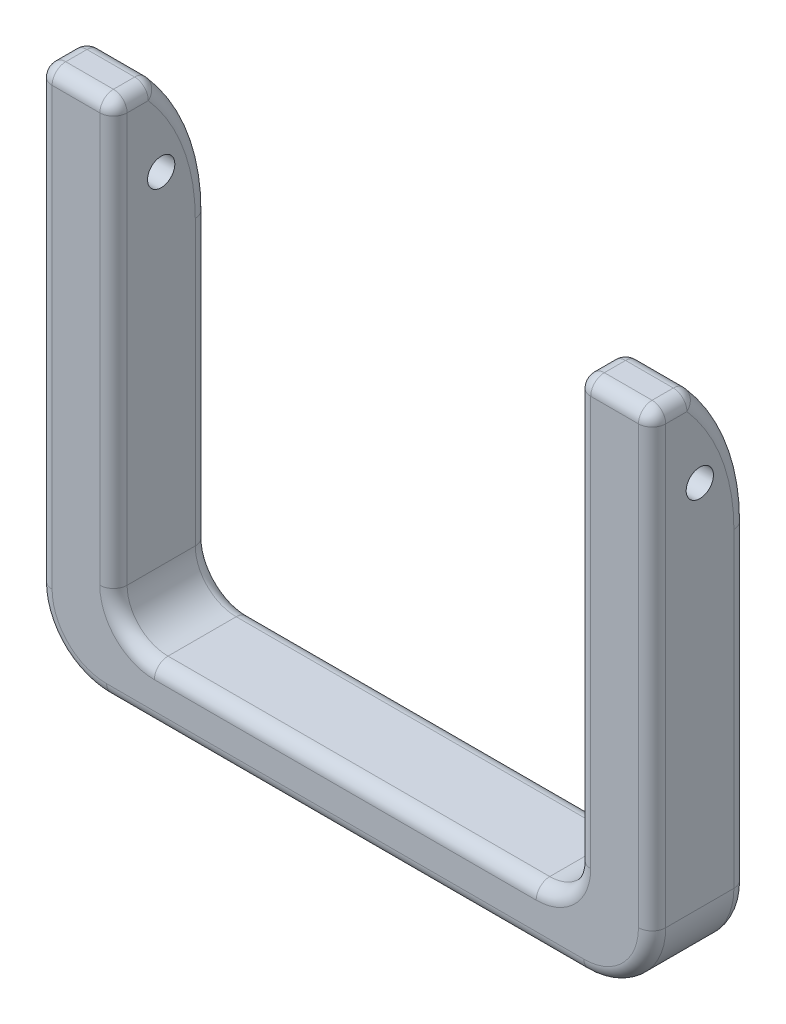
SolidWorks part; units mm, degrees
ref_plane "前视基准面" through (0, 0, 0) normal (0, 0, 1) x (1, 0, 0)
ref_plane "上视基准面" through (0, 0, 0) normal (0, 1, 0) x (1, 0, 0)
ref_plane "右视基准面" through (0, 0, 0) normal (1, 0, 0) x (0, 0, -1)
sketch "草图1" plane through (0, 0, 0) normal (0, 0, 1) x (1, 0, 0)
  line L0 (14, 0) -> (-14, 0)
  line L1 (-17, 3) -> (-17, 34)
  line L2 (-17, 34) -> (-22.5, 34)
  line L3 (-22.5, 34) -> (-22.5, 1)
  line L4 (-17.5, -4) -> (17.5, -4)
  line L5 (0, -4) -> (0, 0) construction
  line L6 (22.5, 34) -> (22.5, 1)
  line L7 (17, 34) -> (22.5, 34)
  line L8 (17, 3) -> (17, 34)
  arc A0 (17, 3) -> (14, 0) centre (14, 3) cw
  arc A1 (-14, 0) -> (-17, 3) centre (-14, 3) cw
  arc A2 (22.5, 1) -> (17.5, -4) centre (17.5, 1) cw
  arc A3 (-22.5, 1) -> (-17.5, -4) centre (-17.5, 1) ccw
  point P13 (17, 0)
  point P16 (-17, 0)
  point P19 (22.5, -4)
  point P22 (-22.5, -4)
  dimension "D5" = 3
  dimension "D6" = 5
  dimension "D1" = 5.5
  dimension "D2" = 38
  dimension "D3" = 4
  dimension "D4" = 17
extrude "凸台-拉伸1" add sketch "草图1" along normal blind 7
sketch "草图3" plane through (-22.5, 0, 0) normal (-1, 0, 0) x (0, 0, 1)
  line L0 (3.5, -4) -> (3.5, 28.7715) construction
  line L2 (7, -4) -> (0, -4) construction
  circle A0 centre (3.5, 28) radius 1
  point P2 (0, 0)
  point P3 (3.5, -4)
  dimension "D1" = 2
  dimension "D2" = 32
extrude "切除-拉伸2" cut sketch "草图3" against normal through all
sketch "草图4" plane through (0, 0, 0) normal (0, 0, -1) x (-1, 0, 0)
  line L4 (-19.75, 34) -> (-19.75, -4.4409) construction
  circle A1 centre (-19.75, 6) radius 1.75
  circle A2 centre (19.75, 6) radius 1.75
  point P1 (0, 0)
  dimension "D1" = 3.5
extrude "切除-拉伸3" cut sketch "草图4" against normal blind 2.5
sketch "草图2" plane through (-22.5, 0, 0) normal (-1, 0, 0) x (0, 0, 1)
  line L1 (0, 34) -> (0, 1) construction
  line L2 (0, 30) -> (4, 34)
  line L3 (7, 34) -> (0, 34) construction
  line L4 (4, 34) -> (7, 34)
  line L5 (7, 34) -> (7, 35.1886)
  line L6 (7, 35.1886) -> (0, 35.1886)
  line L7 (0, 35.1886) -> (0, 30)
  dimension "D1" = 4
  dimension "D2" = 3
extrude "切除-拉伸1" cut sketch "草图2" against normal through all
fillet "圆角2" radius 15 2 edges at (-19.75, 30, 0) (19.75, 30, 0)
fillet "圆角3" radius 1 32 edges at (17, 29.2792, 1.0358) (17, 13.401, 0) (16.1213, 0.8787, 0) (-17, 29.2792, 1.0358) (-17, 13.401, 0) (-16.1213, 0.8787, 0) (-22.5, 29.2792, 1.0358) (-22.5, 12.401, 0) (-21.0355, -2.5355, 0) (0, -4, 0) (21.0355, -2.5355, 0) (22.5, 12.401, 0) (-22.5, 34, 5.5) (-19.75, 34, 4) (-17, 34, 5.5) (0, 0, 0) (-17, 18.5, 7) (-16.1213, 0.8787, 7) (0, 0, 7) (16.1213, 0.8787, 7) (17, 18.5, 7) (22.5, 17.5, 7) (21.0355, -2.5355, 7) (0, -4, 7) (-21.0355, -2.5355, 7) (-22.5, 17.5, 7) (-19.75, 34, 7) (19.75, 34, 7) (17, 34, 5.5) (19.75, 34, 4) (22.5, 34, 5.5) (22.5, 29.2792, 1.0358)
